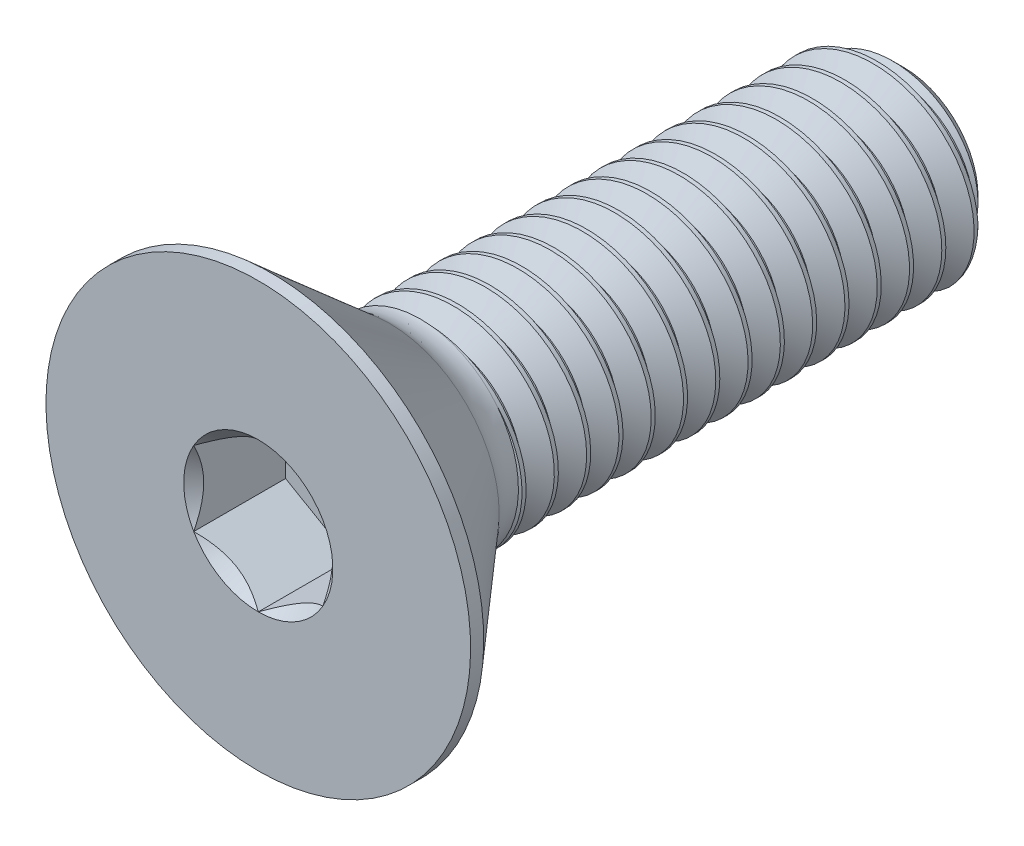
SolidWorks part; units mm, degrees
ref_plane "Front" through (0, 0, 0) normal (0, 0, 1) x (1, 0, 0)
ref_plane "Top" through (0, 0, 0) normal (0, 1, 0) x (1, 0, 0)
ref_plane "Right" through (0, 0, 0) normal (1, 0, 0) x (0, 0, -1)
sketch "Sketch1" plane through (0, 0, 0) normal (1, 0, 0) x (0, 0, -1)
  line L0 (-7.9375, 5.2197) -> (-7.6149, 5.2197) construction
  line L1 (-7.6149, 5.2197) -> (-4.7117, 2.696) construction
  line L2 (-7.9375, 2.413) -> (7.9375, 2.413)
  line L3 (7.9375, 2.413) -> (7.9375, 0)
  line L4 (7.9375, 0) -> (-7.9375, 0)
  line L5 (-7.9375, 0) -> (-7.9375, 5.2197) construction
  line L6 (-7.9375, 5.2197) -> (-7.9375, -5.2197) construction
  line L7 (7.9375, 2.413) -> (7.9375, -2.413) construction
  line L8 (-7.9375, -5.2197) -> (-7.6149, -5.2197) construction
  line L9 (-7.6149, -5.2197) -> (-4.7117, -2.696) construction
  line L11 (-7.9375, 2.413) -> (-7.9375, 0)
  line L12 (-4.7117, 2.696) -> (-4.7117, 0) construction
  line L14 (7.9375, -2.413) -> (7.1437, -2.413) construction
  line L15 (-7.9375, 1.5875) -> (-7.9375, -1.5875)
  arc A2 (-4.7117, 2.696) -> (-3.9549, 2.413) centre (-3.9549, 3.5666) ccw construction
  point P18 (0, 0)
  point P19 (4.4739, -2.413)
  point P24 (-7.9375, 0)
  dimension "Head Diameter" = 10.4394
  dimension "Screw Size Decimal Equivalent" = 4.826
  dimension "Head Height" = 3.2258
  dimension "Countersink Angle" = 82
  dimension "Thread Pitch" = 0.7937
  dimension "D2" = 3.4636
  dimension "Drive Size" = 3.175
  dimension "Length" = 15.875
  dimension "D1" = 0.3226
sketch "Sketch12" plane through (0, 0, 0) normal (1, 0, 0) x (0, 0, -1)
  line L0 (7.9375, 2.413) -> (7.9375, 0) construction
  line L1 (-7.9375, 2.413) -> (7.9375, 2.413) construction
  line L2 (-7.9375, 2.413) -> (-7.9375, 0) construction
  line L3 (7.9375, 0) -> (-7.9375, 0) construction
  line L4 (7.9375, 2.413) -> (7.9375, 0)
  line L5 (-7.9375, 2.413) -> (7.9375, 2.413)
  line L6 (-7.9375, 2.413) -> (-7.9375, 0)
  line L7 (7.9375, 0) -> (-7.9375, 0)
revolve "Revolve3" add sketch "Sketch12" angle 360 about L7
sketch "Sketch3" plane through (0, 0, -7.9375) normal (0, 0, -1) x (-1, 0, 0)
  circle A0 centre (0, 0) radius 2.413
sketch "Sketch7" plane through (0, 0, 0) normal (1, 0, 0) x (0, 0, -1)
  line L0 (-7.9375, 5.2197) -> (-7.6149, 5.2197) construction
  line L1 (-7.6149, 5.2197) -> (-4.7117, 2.696) construction
  line L2 (-7.9375, 5.2197) -> (-7.6149, 5.2197)
  line L3 (-7.6149, 5.2197) -> (-4.7117, 2.696)
  line L6 (-3.9549, 2.413) -> (-3.9549, 0)
  line L7 (-7.9375, 0) -> (-7.9375, 5.2197) construction
  line L8 (-7.9375, 0) -> (-7.9375, 5.2197)
  line L9 (-7.9375, 0) -> (-3.9549, 0)
  line L10 (14.3708, 0) -> (-14.3708, 0) construction
  arc A0 (-4.7117, 2.696) -> (-3.9549, 2.413) centre (-3.9549, 3.5666) ccw construction
  arc A1 (-4.7117, 2.696) -> (-3.9549, 2.413) centre (-3.9549, 3.5666) ccw
revolve "Revolve2" add sketch "Sketch7" angle 360 mid plane about L9
chamfer "Chamfer1" distance 0.5953 angle 45 1 edges at (0, 2.413, -7.9375)
sketch "Sketch5" plane through (0, 0, 7.9375) normal (0, 0, 1) x (1, 0, 0)
  line L0 (0, 0) -> (-1.8331, 0) construction
  line L1 (0, 0) -> (-2.7496, 1.5875) construction
  line L2 (0, 0) -> (-2.7496, -1.5875) construction
  line L6 (0, 1.8331) -> (0, 1.5119) construction
  line L7 (0, 1.5119) -> (0, 1.1906) construction
  line L9 (0, 1.8331) -> (-1.5875, 0.9165)
  line L10 (-1.5875, 0.9165) -> (-1.5875, -0.9165)
  line L11 (-1.5875, -0.9165) -> (0, -1.8331)
  line L12 (0, -1.8331) -> (1.5875, -0.9165)
  line L13 (1.5875, -0.9165) -> (1.5875, 0.9165)
  line L14 (1.5875, 0.9165) -> (0, 1.8331)
  circle A0 centre (0, 0) radius 1.8331 construction
  circle A1 centre (0, 0) radius 1.5119 construction
  circle A2 centre (0, 0) radius 1.1906 construction
  circle A3 centre (0, 0) radius 1.5875 construction
  dimension "D3" = 2.3813
  dimension "D4" = 30
  dimension "D5" = 30
  dimension "Hex" = 3.175
extrude "Cut-Extrude2" cut sketch "Sketch5" against normal blind 2.2581
sketch "Sketch6" plane through (0, 0, 7.9375) normal (0, 0, 1) x (1, 0, 0)
  circle A0 centre (0, 0) radius 1.8331
extrude "Cut-Extrude3" cut sketch "Sketch6" against normal blind 2.2581 draft 45
ref_plane "Plane3" through (0, 0, 3.9549) normal (0, 0, 1) x (1, 0, 0)
split "Split1" trim tools "Plane3" bodies to split 135 resulting bodies 133 134
curve "Helix/Spiral1" pitch 0.7937 height 16.6687 radius 2.413 centre (0, 0, -7.9375) axis (0, 0, 1) start towards (0, 1, 0)
sketch "Sketch2" plane through (0, 0, 0) normal (1, 0, 0) x (0, 0, -1)
  line L0 (7.8879, 2.4989) -> (8.2848, 1.8115) construction
  line L1 (8.2848, 1.8115) -> (8.6816, 2.4989) construction
  line L2 (8.6816, 2.4989) -> (7.8879, 2.4989) construction
  line L3 (8.2848, 1.8115) -> (8.2848, 1.8974) construction
  line L4 (8.2352, 1.8974) -> (8.3344, 1.8974)
  line L5 (8.2848, 2.413) -> (8.2848, 2.4989) construction
  line L6 (7.9375, 2.413) -> (8.632, 2.413) construction
  line L7 (7.9375, -2.413) -> (7.1437, -2.413) construction
  line L8 (8.2352, 1.8974) -> (7.9127, 2.456)
  line L9 (7.9127, 2.456) -> (8.6568, 2.456)
  line L10 (8.6568, 2.456) -> (8.3344, 1.8974)
  point P15 (8.2848, 2.456)
  dimension "D1" = 0.0992
sweep "Cut-Sweep1" cut profiles "Sketch2" path "Helix/Spiral1" align with end faces yes
sketch "Sketch13" plane through (0, 0, 3.9549) normal (0, 0, 1) x (1, 0, 0)
  circle A2 centre (0, 0) radius 2.413
  circle A4 centre (0, 0) radius 2.413
  dimension "D1" = 0
extrude "Boss-Extrude3" add sketch "Sketch13" against normal up to next (11.8924 mm away) draft 60
equation "\"D3@Helix/Spiral1\"=\"Length@Sketch1\"+\"Thread Pitch@Sketch1\""
equation "\"D1@Chamfer1\" = \"D4@Helix/Spiral1\" * .75"
equation "\"D1@Cut-Extrude2\" = \"Head Height@Sketch1\" * .7"
equation "\"D1@Cut-Extrude3\" = \"D1@Cut-Extrude2\""
equation "\"D3@Sketch5\" = \"Hex@Sketch5\" * .75"
equation "\"D4@Helix/Spiral1\"=\"Thread Pitch@Sketch1\""
equation "\"Hex@Sketch5\"=\"Drive Size@Sketch1\""
equation "\"D1@Sketch2\"=\"Thread Pitch@Sketch1\"*0.125"
equation "\"D1@Sketch1\"=\"Head Height@Sketch1\"*.1"
